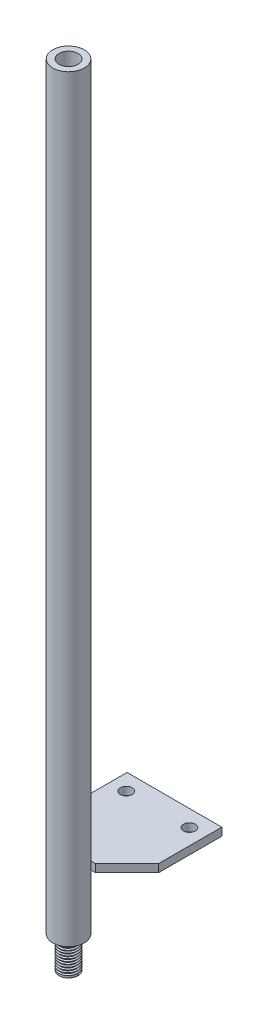
SolidWorks part; units mm, degrees
ref_plane "Front Plane" through (0, 0, 0) normal (0, 0, 1) x (1, 0, 0)
ref_plane "Top Plane" through (0, 0, 0) normal (0, 1, 0) x (1, 0, 0)
ref_plane "Right Plane" through (0, 0, 0) normal (1, 0, 0) x (0, 0, -1)
sketch "Sketch1" plane through (0, 0, 0) normal (0, 1, 0) x (1, 0, 0)
  line L0 (-7.62, 0) -> (-12.7, 0) construction
  circle A0 centre (0, 0) radius 12.7
  circle A1 centre (0, 0) radius 7.62
  dimension "D1" = 25.4
  dimension "D2" = 5.08
extrude "Boss-Extrude1" add sketch "Sketch1" along normal blind 609.6
ref_plane "Plane1" through (0, 12.7, 0) normal (0, -1, 0) x (-1, 0, 0)
sketch "Sketch2" plane through (0, 12.7, 0) normal (0, -1, 0) x (-1, 0, 0)
  circle A0 centre (0, 0) radius 7.62
extrude "Boss-Extrude2" add sketch "Sketch2" along normal blind 38.1
sketch "Sketch5" plane through (0, -25.4, 0) normal (0, -1, 0) x (1, 0, 0)
  circle A0 centre (0, 0) radius 7.62
thread "Thread1" pitch 1.9538 method cut profile "Thread Profile2" start angle 0, offset 0, length 38.1, pitch 1.9538, diameter 15.24
ref_plane "Plane3" through (7.62, -25.4, 0) normal (0, 0, 1) x (1, 0, 0)
sketch "Thread Profile2" plane through (7.62, -25.4, 0) normal (0, 0, 1) x (1, 0, 0)
  line L0 (0, 0) -> (0, 1.9538) construction
  line L11 (0, 0) -> (0, 1.7096)
  line L12 (0, 1.7096) -> (-1.0576, 1.099)
  line L13 (-1.0576, 1.099) -> (-1.0576, 0.6106)
  line L15 (-1.0576, 0.6106) -> (0, 0)
  line L17 (-1.0576, 0.8548) -> (0, 0.8548) construction
  point P2 (0, 0)
  dimension "Pitch" = 1.9538
  dimension "Profile_Angle" = 60
  dimension "Profile_Land" = 0.4885
  dimension "Profile_Height" = 1.0576
ref_plane "Plane4" through (0, 0, 12.7) normal (0, 0, 1) x (1, 0, 0)
ref_plane "Plane5" through (0, 50.8, 0) normal (0, -1, 0) x (-1, 0, 0)
sketch "Sketch10" plane through (0, 50.8, 0) normal (0, -1, 0) x (-1, 0, 0)
  line L0 (0, 0) -> (0, 12.7) construction
  line L1 (-8.9803, 8.9803) -> (0, 0) construction
  line L2 (0, 0) -> (8.9803, 8.9803) construction
  line L3 (-8.9803, 8.9803) -> (-12.7, 8.9803)
  line L4 (-12.7, 8.9803) -> (-38.1, 34.3803)
  line L5 (-38.1, 34.3803) -> (-38.1, 85.1803)
  line L6 (-38.1, 85.1803) -> (38.1, 85.1803)
  line L7 (0, 85.1803) -> (0, 12.7) construction
  line L8 (0, 0) -> (-8.9803, 8.9803) construction
  line L9 (8.9803, 8.9803) -> (0, 0) construction
  line L10 (38.1, 34.3803) -> (38.1, 85.1803)
  line L11 (12.7, 8.9803) -> (38.1, 34.3803)
  line L12 (8.9803, 8.9803) -> (12.7, 8.9803)
  arc A0 (-8.9803, 8.9803) -> (8.9803, 8.9803) centre (0, 0) cw
  circle A1 centre (0, 0) radius 12.7 construction
  dimension "D1" = 45
  dimension "D3" = 76.2
  dimension "D4" = 38.1
  dimension "D5" = 25.4
  dimension "D6" = 25.4
extrude "Boss-Extrude4" add sketch "Sketch10" along normal blind 6.35
sketch "Sketch11" plane through (0, 50.8, 0) normal (0, 1, 0) x (1, 0, 0)
  line L0 (0, 0) -> (0, 71.842) construction
  line L1 (0, 71.842) -> (-25.4, 71.842) construction
  circle A0 centre (-25.4, 71.842) radius 4.7625
  circle A1 centre (25.4, 71.842) radius 4.7625
  dimension "D1" = 9.525
  dimension "D2" = 76.2
  dimension "D3" = 25.4
extrude "Cut-Extrude2" cut sketch "Sketch11" against normal up to next
